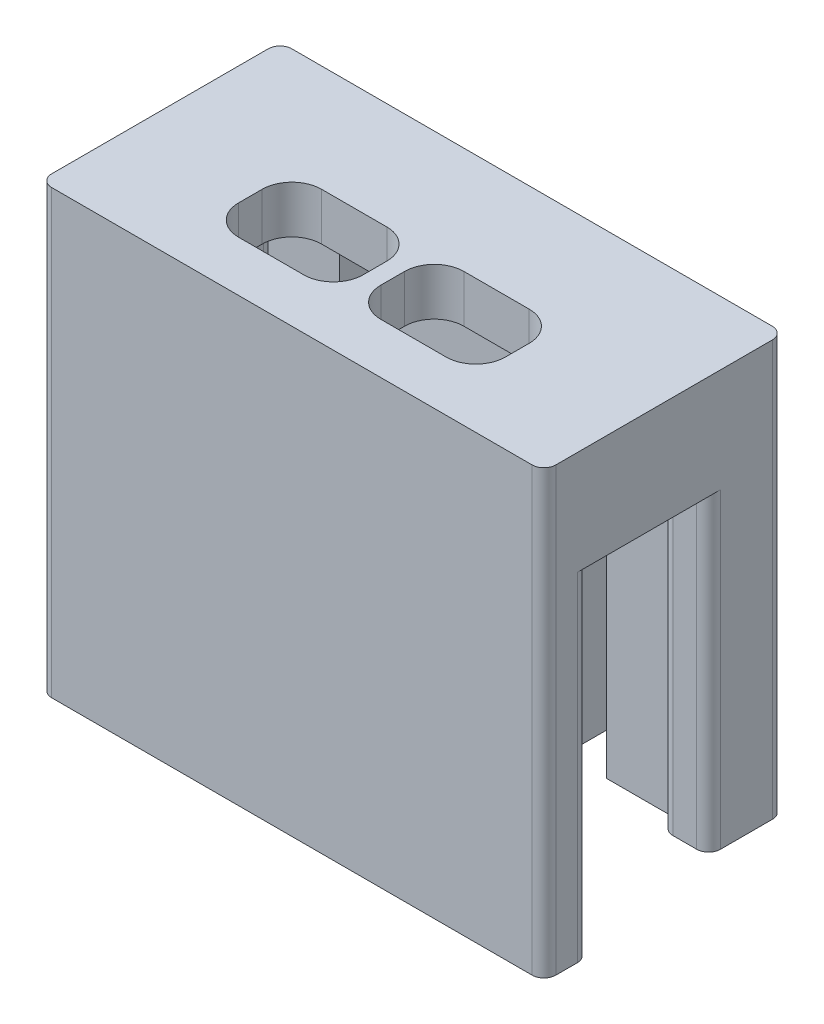
SolidWorks part; units mm, degrees
note: The reader was unsure of these and kept them because the rebuilt part matched: shared geometry of "Sketch1<3>".
ref_plane "Front Plane" through (0, 0, 0) normal (0, 0, 1) x (1, 0, 0)
ref_plane "Top Plane" through (0, 0, 0) normal (0, 1, 0) x (1, 0, 0)
ref_plane "Right Plane" through (0, 0, 0) normal (1, 0, 0) x (0, 0, -1)
sketch "Sketch1" plane through (0, 0, 0) normal (0, 0, 1) x (1, 0, 0)
  line L0 (-42.5, 40) -> (42.5, 40)
  line L1 (-32.5, -30) -> (32.5, -30)
  line L2 (-32.5, -30) -> (-32.5, 30)
  line L3 (-32.5, 30) -> (32.5, 30)
  line L4 (32.5, -30) -> (32.5, 30)
  line L5 (-32.5, -30) -> (32.5, 30) construction
  line L6 (-32.5, 30) -> (32.5, -30) construction
  line L7 (42.5, -30) -> (42.5, 40)
  line L9 (-42.5, -30) -> (-42.5, 40)
  line L10 (-32.5, -30) -> (-42.5, -30)
  line L11 (32.5, -30) -> (42.5, -30)
  line L12 (42.5, -40) -> (42.5, 40) construction
  line L13 (-42.5, -40) -> (42.5, -40) construction
  line L14 (-42.5, -40) -> (-42.5, 40) construction
  point P0 (0, 0)
  point P13 (42.5, -29.9261)
  point P14 (-42.5, -29.996)
  dimension "D1" = 65
  dimension "D2" = 60
  dimension "D3" = 10
extrude "Boss-Extrude1" add sketch "Sketch1" along normal blind 10 contours L1 L4 L3 L2 | L4 L11 L7 L0 L9 L10 L2 L3
sketch "Sketch6" plane through (0, 0, 10) normal (0, 0, 1) x (1, 0, 0)
  line L0 (0, -30) -> (0, 17.5) construction
  line L1 (-42.5, -30) -> (42.5, -30) construction
  line L2 (-42.5, 2.5577) -> (42.5, 2.5577) construction
  line L3 (-42.5, -30) -> (-42.5, 40) construction
  line L4 (42.5, -30) -> (42.5, 40) construction
  line L5 (7.5, 17.5) -> (0, 17.5) construction
  line L6 (7.5, 17.5) -> (17.5, 17.5)
  line L7 (7.5, 17.5) -> (7.5, 16.5)
  line L8 (7.5, 16.5) -> (17.5, 16.5)
  line L9 (17.5, 17.5) -> (17.5, 16.5)
  line L10 (-7.5, 16.5) -> (-17.5, 16.5)
  line L11 (-17.5, 17.5) -> (-17.5, 16.5)
  line L12 (-7.5, 17.5) -> (-17.5, 17.5)
  line L13 (-7.5, 17.5) -> (-7.5, 16.5)
  line L14 (-17.5, 16.5) -> (17.5, 16.5) construction
  point P7 (0, 2.5577)
  dimension "D1" = 47.5
  dimension "D2" = 1
  dimension "D3" = 10
extrude "Boss-Extrude6" add sketch "Sketch6" along normal blind 1
sketch "Sketch7" plane through (17.5, 0, 0) normal (1, 0, 0) x (0, 0, -1)
  line L0 (-10, 16.5) -> (-11, 17.5)
  line L4 (-10, 16.5) -> (-10, 17.5)
  line L5 (-10, 17.5) -> (-11, 17.5)
  line L6 (-11, 17.5) -> (-11, 16.5)
  line L7 (-11, 16.5) -> (-10, 16.5)
  line L8 (-10, 16.5) -> (-10, 17.5)
  line L9 (-10, 17.5) -> (-11, 17.5)
  line L10 (-11, 17.5) -> (-11, 16.5)
  line L11 (-11, 16.5) -> (-10, 16.5)
  point P2 (-15, 17.3041)
  line M7 (-11, 17.5) -> (-11, 16.5)
  line M8 (-11, 16.5) -> (-10, 16.5)
  dimension "D1" = 0
extrude "Cut-Extrude2" cut sketch "Sketch7" against normal through all and the other way blind 1 contours L0 M8 M7
extrude "Boss-Extrude2" add sketch "Sketch1<3>" along normal blind 33 contours L4 L11 L7 L0 L9 L10 L2 L3
sketch "Sketch1<3>" plane through (0, 0, 0) normal (0, 0, 1) x (1, 0, 0) same geometry as "Sketch1"
sketch "Sketch2" plane through (-42.5, 0, 0) normal (-1, 0, 0) x (0, 0, 1)
  line L0 (0, 2.4909) -> (12.75, 2.4909) construction
  line L1 (33, -30) -> (12.75, -30)
  line L2 (33, -30) -> (33, 22.5)
  line L3 (33, 22.5) -> (12.75, 22.5)
  line L4 (12.75, -30) -> (12.75, 22.5)
  line L5 (0, -30) -> (0, 40) construction
  line L6 (22.1988, 40) -> (22.1988, 22.5) construction
  line L7 (33, 40) -> (0, 40) construction
  dimension "D2" = 12.75
extrude "Cut-Extrude1" cut sketch "Sketch2" against normal through all
sketch "Sketch3" plane through (0, 0, 33) normal (0, 0, 1) x (1, 0, 0)
  line L8 (32.5, 22.5) -> (42.5, 22.5)
  line L9 (42.5, 22.5) -> (42.5, 40)
  line L10 (42.5, 40) -> (-42.5, 40)
  line L11 (-42.5, 40) -> (-42.5, 22.5)
  line L12 (-42.5, 22.5) -> (-32.5, 22.5)
  line L13 (-32.5, 22.5) -> (-32.5, 30)
  line L14 (-32.5, 30) -> (32.5, 30)
  line L15 (32.5, 30) -> (32.5, 22.5)
  line L16 (32.5, 22.5) -> (42.5, 22.5)
  line L17 (42.5, 22.5) -> (42.5, 40)
  line L18 (42.5, 40) -> (-42.5, 40)
  line L19 (-42.5, 40) -> (-42.5, 22.5)
  line L20 (-42.5, 22.5) -> (-32.5, 22.5)
  line L21 (-32.5, 22.5) -> (-32.5, 30)
  line L22 (-32.5, 30) -> (32.5, 30)
  line L23 (32.5, 30) -> (32.5, 22.5)
  dimension "D1" = 0
extrude "Boss-Extrude3" add sketch "Sketch3" along normal blind 7.5
sketch "Sketch4" plane through (0, 40, 0) normal (0, 1, 0) x (1, 0, 0)
  line L0 (42.5, -40.5) -> (42.5, 0) construction
  line L1 (-42.5, -40.5) -> (42.5, -40.5)
  line L2 (-42.5, -40.5) -> (-42.5, -40.397)
  line L3 (-42.5, -40.397) -> (42.5, -40.397)
  line L4 (42.5, -40.5) -> (42.5, -40.397)
  point P7 (0, 0)
sketch "Sketch5" plane through (0, 40, 0) normal (0, 1, 0) x (1, 0, 0)
  line L0 (42.5, -40.5) -> (42.5, 0) construction
  line L1 (-42.5, -40.5) -> (42.5, -40.5)
  line L2 (-42.5, -40.5) -> (-42.5, -32.8886)
  line L3 (-42.5, -32.8886) -> (42.5, -32.8886)
  line L4 (42.5, -40.5) -> (42.5, -32.8886)
extrude "Boss-Extrude5" add sketch "Sketch5" against normal up to vertex (70 mm away)
sketch "Sketch8" plane through (0, 30, 0) normal (0, -1, 0) x (1, 0, 0)
  line L4 (32.5, 10) -> (32.5, 32.8886)
  line L5 (32.5, 32.8886) -> (-32.5, 32.8886)
  line L6 (-32.5, 32.8886) -> (-32.5, 10)
  line L7 (-32.5, 10) -> (32.5, 10)
  line L8 (32.5, 10) -> (32.5, 32.8886)
  line L9 (32.5, 32.8886) -> (-32.5, 32.8886)
  line L10 (-32.5, 32.8886) -> (-32.5, 10)
  line L11 (-32.5, 10) -> (32.5, 10)
  dimension "D1" = 0
extrude "Cut-Extrude3" cut sketch "Sketch8" against normal blind 2
sketch "Sketch9" plane through (32.5, 0, 0) normal (-1, 0, 0) x (0, 0, 1)
  line L6 (32.8886, 22.5) -> (32.8886, 32)
  line L7 (32.8886, 32) -> (10, 32)
  line L8 (10, 32) -> (10, -30)
  line L9 (10, -30) -> (12.75, -30)
  line L10 (12.75, -30) -> (12.75, 22.5)
  line L11 (12.75, 22.5) -> (32.8886, 22.5)
  line L12 (32.8886, 22.5) -> (32.8886, 32)
  line L13 (32.8886, 32) -> (10, 32)
  line L14 (10, 32) -> (10, -30)
  line L15 (10, -30) -> (12.75, -30)
  line L16 (12.75, -30) -> (12.75, 22.5)
  line L17 (12.75, 22.5) -> (32.8886, 22.5)
  dimension "D1" = 0
extrude "Cut-Extrude4" cut sketch "Sketch9" against normal blind 2
mirror "Mirror1" about plane through (0, 0, 0) normal (1, 0, 0) of "Cut-Extrude4"
sketch "Sketch10" plane through (0, 40, 0) normal (0, 1, 0) x (1, 0, 0)
  line L0 (42.5, -18.1166) -> (19.5, -18.1166) construction
  line L1 (4.5, -21) -> (19.5, -21)
  line L2 (4.5, -21) -> (4.5, -29)
  line L3 (4.5, -29) -> (19.5, -29)
  line L4 (19.5, -21) -> (19.5, -29)
  line L5 (42.5, -40.5) -> (42.5, 0) construction
  line L6 (12, -21) -> (12, 0) construction
  line L7 (-42.5, 0) -> (42.5, 0) construction
  dimension "D1" = 23
  dimension "D2" = 15
  dimension "D3" = 8
  dimension "D4" = 21
sketch "Sketch11" plane through (0, 0, 0) normal (0, 0, -1) x (-1, 0, 0)
  line L1 (-22.5, 30) -> (-15.5, 30)
  line L2 (-22.5, 30) -> (-22.5, -30)
  line L3 (-22.5, -30) -> (-15.5, -30)
  line L4 (-15.5, 30) -> (-15.5, -30)
  line L8 (42.5, -30) -> (-42.5, -30) construction
  line L9 (-22.5, 9.301) -> (-42.5, 9.301) construction
  line L12 (-42.5, -30) -> (-42.5, 40) construction
  line L13 (-22.5, 9.301) -> (-15.5, 9.301) construction
  point P6 (-16.5, 9.6841)
  point P7 (-21.5, 9.6613)
  point P11 (0, 0)
  point P13 (-21.5, 9.6648)
  point P16 (-19, 9.301)
  point P17 (0, 0)
  point P18 (-21.5, 9.1112)
  point P19 (0, 0)
  point P20 (0, 0)
  point P21 (-21.4575, 9.6356)
  point P22 (-13.9942, 9.301)
  point P23 (0, 0)
  dimension "D1" = 60
  dimension "D2" = 7
extrude "Cut-Extrude5" cut sketch "Sketch11" along a picked direction on the side against the normal up to next (12.75 mm away)
mirror "Mirror2" about plane through (0, 0, 0) normal (1, 0, 0) of "Cut-Extrude5"
extrude "Cut-Extrude6" cut sketch "Sketch10" against normal up to next
mirror "Mirror4" about plane through (0, 0, 0) normal (1, 0, 0) of "Cut-Extrude6"
fillet "Fillet1" radius 2 18 edges at (34.5, -3.75, 12.75) (-34.5, -3.75, 12.75) (-42.5, -3.75, 12.75) (-42.5, -3.75, 32.8886) (42.5, -3.75, 32.8886) (42.5, -3.75, 12.75) (42.5, 5, 0) (42.5, 5, 40.5) (-42.5, 5, 0) (-42.5, 5, 40.5) (-4.5, 36, 29) (-4.5, 36, 21) (-19.5, 36, 21) (-19.5, 36, 29) (4.5, 36, 29) (4.5, 36, 21) (19.5, 36, 29) (19.5, 36, 21)
sketch "Sketch12" plane through (0, -30, 0) normal (0, -1, 0) x (1, 0, 0)
  line L4 (-42.5, 38.5) -> (-42.5, 34.8886)
  line L5 (-40.5, 32.8886) -> (40.5, 32.8886)
  line L6 (42.5, 34.8886) -> (42.5, 38.5)
  line L7 (40.5, 40.5) -> (-40.5, 40.5)
  line L8 (-42.5, 38.5) -> (-42.5, 34.8886)
  line L9 (-40.5, 32.8886) -> (40.5, 32.8886)
  line L10 (42.5, 34.8886) -> (42.5, 38.5)
  line L11 (40.5, 40.5) -> (-40.5, 40.5)
  arc A4 (-42.5, 34.8886) -> (-40.5, 32.8886) centre (-40.5, 34.8886) ccw
  arc A5 (40.5, 32.8886) -> (42.5, 34.8886) centre (40.5, 34.8886) ccw
  arc A6 (42.5, 38.5) -> (40.5, 40.5) centre (40.5, 38.5) ccw
  arc A7 (-40.5, 40.5) -> (-42.5, 38.5) centre (-40.5, 38.5) ccw
  arc A8 (-42.5, 34.8886) -> (-40.5, 32.8886) centre (-40.5, 34.8886) ccw
  arc A9 (40.5, 32.8886) -> (42.5, 34.8886) centre (40.5, 34.8886) ccw
  arc A10 (42.5, 38.5) -> (40.5, 40.5) centre (40.5, 38.5) ccw
  arc A11 (-40.5, 40.5) -> (-42.5, 38.5) centre (-40.5, 38.5) ccw
  dimension "D1" = 0
extrude "Boss-Extrude7" add sketch "Sketch12" along normal blind 4.5
sketch "Sketch14" plane through (0, 40, 0) normal (0, 1, 0) x (1, 0, 0)
  line L0 (-6.5, -29) -> (-17.5, -29) construction
  line L1 (-19.5, -27) -> (-19.5, -23) construction
  line L2 (-17.5, -21) -> (-6.5, -21) construction
  line L3 (-4.5, -23) -> (-4.5, -27) construction
  line L4 (19.5, -27) -> (19.5, -23) construction
  line L5 (6.5, -29) -> (17.5, -29) construction
  line L6 (4.5, -23) -> (4.5, -27) construction
  line L7 (17.5, -21) -> (6.5, -21) construction
  line L8 (-6.5, -29) -> (-17.5, -29)
  line L9 (-19.5, -27) -> (-19.5, -23)
  line L10 (-17.5, -21) -> (-6.5, -21)
  line L11 (-4.5, -23) -> (-4.5, -27)
  line L12 (19.5, -27) -> (19.5, -23)
  line L13 (6.5, -29) -> (17.5, -29)
  line L14 (4.5, -23) -> (4.5, -27)
  line L15 (17.5, -21) -> (6.5, -21)
  line L16 (17.5, -18) -> (6.5, -18)
  line L17 (1.5, -23) -> (1.5, -27)
  line L18 (6.5, -32) -> (17.5, -32)
  line L19 (22.5, -27) -> (22.5, -23)
  line L20 (-1.5, -23) -> (-1.5, -27)
  line L21 (-17.5, -18) -> (-6.5, -18)
  line L22 (-22.5, -27) -> (-22.5, -23)
  line L23 (-6.5, -32) -> (-17.5, -32)
  arc A0 (-6.5, -29) -> (-4.5, -27) centre (-6.5, -27) ccw construction
  arc A1 (-19.5, -27) -> (-17.5, -29) centre (-17.5, -27) ccw construction
  arc A2 (-17.5, -21) -> (-19.5, -23) centre (-17.5, -23) ccw construction
  arc A3 (-4.5, -23) -> (-6.5, -21) centre (-6.5, -23) ccw construction
  arc A4 (19.5, -23) -> (17.5, -21) centre (17.5, -23) ccw construction
  arc A5 (17.5, -29) -> (19.5, -27) centre (17.5, -27) ccw construction
  arc A6 (4.5, -27) -> (6.5, -29) centre (6.5, -27) ccw construction
  arc A7 (6.5, -21) -> (4.5, -23) centre (6.5, -23) ccw construction
  arc A8 (-6.5, -29) -> (-4.5, -27) centre (-6.5, -27) ccw
  arc A9 (-19.5, -27) -> (-17.5, -29) centre (-17.5, -27) ccw
  arc A10 (-17.5, -21) -> (-19.5, -23) centre (-17.5, -23) ccw
  arc A11 (-4.5, -23) -> (-6.5, -21) centre (-6.5, -23) ccw
  arc A12 (19.5, -23) -> (17.5, -21) centre (17.5, -23) ccw
  arc A13 (17.5, -29) -> (19.5, -27) centre (17.5, -27) ccw
  arc A14 (4.5, -27) -> (6.5, -29) centre (6.5, -27) ccw
  arc A15 (6.5, -21) -> (4.5, -23) centre (6.5, -23) ccw
  arc A16 (22.5, -23) -> (17.5, -18) centre (17.5, -23) ccw
  arc A17 (6.5, -18) -> (1.5, -23) centre (6.5, -23) ccw
  arc A18 (1.5, -27) -> (6.5, -32) centre (6.5, -27) ccw
  arc A19 (17.5, -32) -> (22.5, -27) centre (17.5, -27) ccw
  arc A20 (-6.5, -32) -> (-1.5, -27) centre (-6.5, -27) ccw
  arc A21 (-1.5, -23) -> (-6.5, -18) centre (-6.5, -23) ccw
  arc A22 (-17.5, -18) -> (-22.5, -23) centre (-17.5, -23) ccw
  arc A23 (-22.5, -27) -> (-17.5, -32) centre (-17.5, -27) ccw
  dimension "D1" = 3
extrude "Cut-Extrude8" cut sketch "Sketch14" against normal up to next
